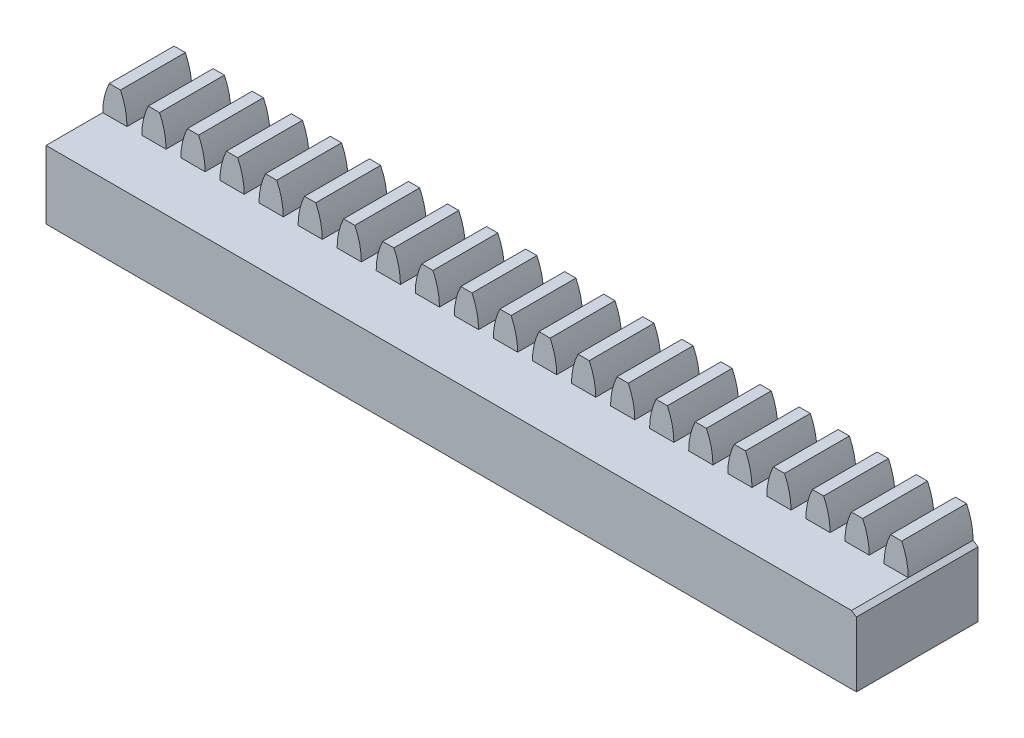
SolidWorks part; units mm, degrees
material "ABS"
ref_plane "Plano frontal" through (0, 0, 0) normal (0, 0, 1) x (1, 0, 0)
ref_plane "Plano superior" through (0, 0, 0) normal (0, 1, 0) x (1, 0, 0)
ref_plane "Plano direito" through (0, 0, 0) normal (1, 0, 0) x (0, 0, -1)
sketch "Esboço1" plane through (0, 0, 0) normal (0, 0, 1) x (1, 0, 0)
  line L0 (-1.7112, 4.5297) -> (-1.0175, 4.5297)
  line L1 (0.6988, 4.5297) -> (1.3925, 4.5297)
  line L2 (0.2978, 2.7713) -> (2.7078, 2.7713)
  line L3 (-2.1122, 2.7713) -> (0.2978, 2.7713)
  line L4 (3.1088, 4.5297) -> (3.8025, 4.5297)
  line L5 (2.7078, 2.7713) -> (5.1178, 2.7713)
  line L6 (5.5188, 4.5297) -> (6.2125, 4.5297)
  line L7 (5.1178, 2.7713) -> (7.5278, 2.7713)
  line L8 (7.9288, 4.5297) -> (8.6225, 4.5297)
  line L9 (7.5278, 2.7713) -> (9.9378, 2.7713)
  line L10 (10.3388, 4.5297) -> (11.0325, 4.5297)
  line L11 (9.9378, 2.7713) -> (12.3478, 2.7713)
  line L12 (12.7488, 4.5297) -> (13.4425, 4.5297)
  line L13 (12.3478, 2.7713) -> (14.7578, 2.7713)
  line L14 (15.1588, 4.5297) -> (15.8525, 4.5297)
  line L15 (14.7578, 2.7713) -> (17.1678, 2.7713)
  line L16 (17.5688, 4.5297) -> (18.2625, 4.5297)
  line L17 (17.1678, 2.7713) -> (19.5778, 2.7713)
  line L18 (19.9788, 4.5297) -> (20.6725, 4.5297)
  line L19 (19.5778, 2.7713) -> (21.9878, 2.7713)
  line L20 (22.3888, 4.5297) -> (23.0825, 4.5297)
  line L21 (21.9878, 2.7713) -> (24.3978, 2.7713)
  line L22 (24.7988, 4.5297) -> (25.4925, 4.5297)
  line L23 (24.3978, 2.7713) -> (26.8078, 2.7713)
  line L24 (27.2088, 4.5297) -> (27.9025, 4.5297)
  line L25 (26.8078, 2.7713) -> (29.2178, 2.7713)
  line L26 (29.6188, 4.5297) -> (30.3125, 4.5297)
  line L27 (29.2178, 2.7713) -> (31.6278, 2.7713)
  line L28 (32.0288, 4.5297) -> (32.7225, 4.5297)
  line L29 (31.6278, 2.7713) -> (34.0378, 2.7713)
  line L30 (34.4388, 4.5297) -> (35.1325, 4.5297)
  line L31 (34.0378, 2.7713) -> (36.4478, 2.7713)
  line L32 (36.8488, 4.5297) -> (37.5425, 4.5297)
  line L33 (36.4478, 2.7713) -> (38.8578, 2.7713)
  line L34 (39.2588, 4.5297) -> (39.9525, 4.5297)
  line L35 (38.8578, 2.7713) -> (41.2678, 2.7713)
  line L36 (41.6688, 4.5297) -> (42.3625, 4.5297)
  line L37 (41.2678, 2.7713) -> (43.6778, 2.7713)
  line L38 (44.0788, 4.5297) -> (44.7725, 4.5297)
  line L39 (43.6778, 2.7713) -> (46.0878, 2.7713)
  line L40 (46.4888, 4.5297) -> (47.1825, 4.5297)
  line L41 (46.0878, 2.7713) -> (47.5834, 2.7713)
  line L42 (47.8878, -1.4287) -> (47.8878, 2.5713)
  line L43 (47.8878, 2.5713) -> (47.5834, 2.7713)
  line L124 (-2.1122, 2.7713) -> (-2.1122, -1.4287)
  line L127 (-2.1122, -1.4287) -> (47.8878, -1.4287)
  arc A0 (-1.7112, 4.5297) -> (-2.1122, 2.7713) centre (1.944, 2.7713) ccw
  arc A1 (-1.0175, 4.5297) -> (-0.6166, 2.7713) centre (-4.6728, 2.7713) cw
  arc A2 (0.6988, 4.5297) -> (0.2978, 2.7713) centre (4.354, 2.7713) ccw
  arc A3 (1.3925, 4.5297) -> (1.7934, 2.7713) centre (-2.2628, 2.7713) cw
  arc A4 (3.1088, 4.5297) -> (2.7078, 2.7713) centre (6.764, 2.7713) ccw
  arc A5 (3.8025, 4.5297) -> (4.2034, 2.7713) centre (0.1472, 2.7713) cw
  arc A6 (5.5188, 4.5297) -> (5.1178, 2.7713) centre (9.174, 2.7713) ccw
  arc A7 (6.2125, 4.5297) -> (6.6134, 2.7713) centre (2.5572, 2.7713) cw
  arc A8 (7.9288, 4.5297) -> (7.5278, 2.7713) centre (11.584, 2.7713) ccw
  arc A9 (8.6225, 4.5297) -> (9.0234, 2.7713) centre (4.9672, 2.7713) cw
  arc A10 (10.3388, 4.5297) -> (9.9378, 2.7713) centre (13.994, 2.7713) ccw
  arc A11 (11.0325, 4.5297) -> (11.4334, 2.7713) centre (7.3772, 2.7713) cw
  arc A12 (12.7488, 4.5297) -> (12.3478, 2.7713) centre (16.404, 2.7713) ccw
  arc A13 (13.4425, 4.5297) -> (13.8434, 2.7713) centre (9.7872, 2.7713) cw
  arc A14 (15.1588, 4.5297) -> (14.7578, 2.7713) centre (18.814, 2.7713) ccw
  arc A15 (15.8525, 4.5297) -> (16.2534, 2.7713) centre (12.1972, 2.7713) cw
  arc A16 (17.5688, 4.5297) -> (17.1678, 2.7713) centre (21.224, 2.7713) ccw
  arc A17 (18.2625, 4.5297) -> (18.6634, 2.7713) centre (14.6072, 2.7713) cw
  arc A18 (19.9788, 4.5297) -> (19.5778, 2.7713) centre (23.634, 2.7713) ccw
  arc A19 (20.6725, 4.5297) -> (21.0734, 2.7713) centre (17.0172, 2.7713) cw
  arc A20 (22.3888, 4.5297) -> (21.9878, 2.7713) centre (26.044, 2.7713) ccw
  arc A21 (23.0825, 4.5297) -> (23.4834, 2.7713) centre (19.4272, 2.7713) cw
  arc A22 (24.7988, 4.5297) -> (24.3978, 2.7713) centre (28.454, 2.7713) ccw
  arc A23 (25.4925, 4.5297) -> (25.8934, 2.7713) centre (21.8372, 2.7713) cw
  arc A24 (27.2088, 4.5297) -> (26.8078, 2.7713) centre (30.864, 2.7713) ccw
  arc A25 (27.9025, 4.5297) -> (28.3034, 2.7713) centre (24.2472, 2.7713) cw
  arc A26 (29.6188, 4.5297) -> (29.2178, 2.7713) centre (33.274, 2.7713) ccw
  arc A27 (30.3125, 4.5297) -> (30.7134, 2.7713) centre (26.6572, 2.7713) cw
  arc A28 (32.0288, 4.5297) -> (31.6278, 2.7713) centre (35.684, 2.7713) ccw
  arc A29 (32.7225, 4.5297) -> (33.1234, 2.7713) centre (29.0672, 2.7713) cw
  arc A30 (34.4388, 4.5297) -> (34.0378, 2.7713) centre (38.094, 2.7713) ccw
  arc A31 (35.1325, 4.5297) -> (35.5334, 2.7713) centre (31.4772, 2.7713) cw
  arc A32 (36.8488, 4.5297) -> (36.4478, 2.7713) centre (40.504, 2.7713) ccw
  arc A33 (37.5425, 4.5297) -> (37.9434, 2.7713) centre (33.8872, 2.7713) cw
  arc A34 (39.2588, 4.5297) -> (38.8578, 2.7713) centre (42.914, 2.7713) ccw
  arc A35 (39.9525, 4.5297) -> (40.3534, 2.7713) centre (36.2972, 2.7713) cw
  arc A36 (41.6688, 4.5297) -> (41.2678, 2.7713) centre (45.324, 2.7713) ccw
  arc A37 (42.3625, 4.5297) -> (42.7634, 2.7713) centre (38.7072, 2.7713) cw
  arc A38 (44.0788, 4.5297) -> (43.6778, 2.7713) centre (47.734, 2.7713) ccw
  arc A39 (44.7725, 4.5297) -> (45.1734, 2.7713) centre (41.1172, 2.7713) cw
  arc A40 (46.4888, 4.5297) -> (46.0878, 2.7713) centre (50.144, 2.7713) ccw
  arc A41 (47.1825, 4.5297) -> (47.5834, 2.7713) centre (43.5272, 2.7713) cw
  dimension "D1" = 0.9144
  dimension "D2" = 50
  dimension "D4" = 0.6937
  dimension "D5" = 1.4956
  dimension "D10" = 4.2
extrude "Ressalto-extrusão1" add sketch "Esboço1" along normal mid plane 4 contours A1 L0 A0 L3 | A3 L1 A2 L2 | A5 L4 A4 L5 | A7 L6 A6 L7 | A9 L8 A8 L9 | A11 L10 A10 L11 | A13 L12 A12 L13 | A15 L14 A14 L15 | A17 L16 A16 L17 | A19 L18 A18 L19 | A21 L20 A20 L21 | A23 L22 A22 L23 | A25 L24 A24 L25 | A27 L26 A26 L27 | A29 L28 A28 L29 | A31 L30 A30 L31 | A33 L32 A32 L33 | A35 L34 A34 L35 | A37 L36 A36 L37 | A39 L38 A38 L39 | A41 L40 A40 L41 region at (-1.3644, 3.5563, 0) region at (1.0456, 3.5563, 0) region at (3.4556, 3.5563, 0) region at (46.8356, 3.5563, 0) region at (5.8656, 3.5563, 0) region at (44.4256, 3.5563, 0) region at (8.2756, 3.5563, 0) region at (42.0156, 3.5563, 0) region at (10.6856, 3.5563, 0) region at (39.6056, 3.5563, 0) region at (13.0956, 3.5563, 0) region at (37.1956, 3.5563, 0) region at (15.5056, 3.5563, 0) region at (34.7856, 3.5563, 0) region at (17.9156, 3.5563, 0) region at (32.3756, 3.5563, 0) region at (20.3256, 3.5563, 0) region at (29.9656, 3.5563, 0) region at (22.7356, 3.5563, 0) region at (27.5556, 3.5563, 0) region at (25.1456, 3.5563, 0)
extrude "Ressalto-extrusão2" add sketch "Esboço1<7>" along normal blind 5.5 and the other way blind 2 contours L124 L127 L42 L43 L41 L39 L37 L35 L33 L31 L29 L27 L25 L23 L21 L19 L17 L15 L13 L11 L9 L7 L5 L2 L3 region at (22.8842, 0.671, 0)
sketch "Esboço1<7>" plane through (0, 0, 0) normal (0, 0, 1) x (1, 0, 0) same geometry as "Esboço1"
